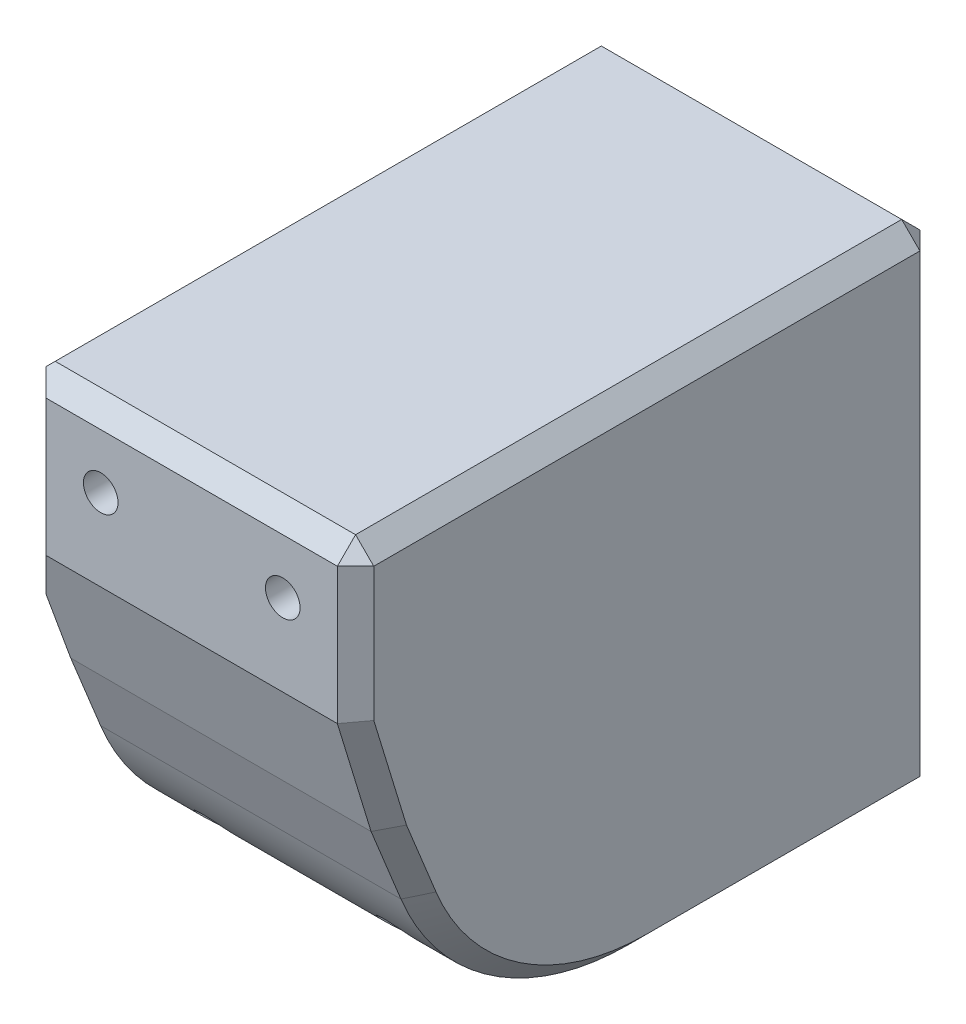
SolidWorks part; units mm, degrees
material "丙烯酸(中高冲击)"
ref_plane "前视基准面" through (0, 0, 0) normal (0, 0, 1) x (1, 0, 0)
ref_plane "上视基准面" through (0, 0, 0) normal (0, 1, 0) x (1, 0, 0)
ref_plane "右视基准面" through (0, 0, 0) normal (1, 0, 0) x (0, 0, -1)
sketch "草图1" plane through (0, 0, 0) normal (1, 0, 0) x (0, 0, -1)
  line L1 (-16, -13.5) -> (16, -13.5)
  line L2 (-16, -13.5) -> (-16, 13.5)
  line L3 (-16, 13.5) -> (16, 13.5)
  line L4 (16, -13.5) -> (16, 13.5)
  line L5 (-16, -13.5) -> (16, 13.5) construction
  line L6 (-16, 13.5) -> (16, -13.5) construction
  point P0 (0, 0)
  dimension "D1" = 32
  dimension "D2" = 27
extrude "凸台-拉伸1" add sketch "草图1" along normal blind 18
sketch "草图2" plane through (0, 0, 0) normal (-1, 0, 0) x (0, 0, 1)
  line L0 (0, 13.5) -> (0, -16.8118) construction
  line L1 (-16, 13.5) -> (16, 13.5) construction
  line L2 (-16, 0) -> (32.6294, 0) construction
  line L3 (-16, -13.5) -> (-16, 13.5) construction
  circle A0 centre (0, 0) radius 12.5
  dimension "D1" = 25
extrude "切除-拉伸1" cut sketch "草图2" against normal blind 13.5
sketch "草图3" plane through (13.5, 0, 0) normal (-1, 0, 0) x (0, 0, 1)
  circle A0 centre (0, 0) radius 3.5
  dimension "D1" = 7
extrude "切除-拉伸2" cut sketch "草图3" against normal offset from surface (4 mm away) 0.5 up to face at (18, 0, 0)
sketch "草图4" plane through (0, 0, -16) normal (0, 0, -1) x (-1, 0, 0)
  line L0 (-17.7262, 0) -> (0.9192, 0) construction
  line L1 (-9, 13.5) -> (-9, -17.0327) construction
  line L2 (-18, 13.5) -> (0, 13.5) construction
  line L3 (-18, -13.5) -> (-18, 13.5) construction
  circle A0 centre (-14, 9.5) radius 0.95
  circle A1 centre (-4, 9.5) radius 0.95
  circle A2 centre (-4, -9.5) radius 0.95
  circle A3 centre (-14, -9.5) radius 0.95
  dimension "D1" = 1.9
  dimension "D2" = 4
  dimension "D3" = 4
extrude "切除-拉伸3" cut sketch "草图4" against normal through all
sketch "草图6" plane through (0, 0, 0) normal (-1, 0, 0) x (0, 0, 1)
  line L0 (16, -13.5) -> (16, 3.5151)
  line L2 (16, -13.5) -> (0, -13.5)
  line L3 (16, -13.5) -> (-16, -13.5) construction
  line L5 (16, 3.5151) -> (12.507, -5.0817)
  line L6 (16, 13.5) -> (16, -13.5) construction
  arc A0 (0, -13.5) -> (12.507, -5.0817) centre (0, 0) ccw
extrude "切除-拉伸4" cut sketch "草图6" against normal through all
chamfer "倒角2" distance 1.5 angle 17 1 edges at (9, 3.5151, 16) first distance on face at (4.95, 9.5, 16)
chamfer "倒角3" distance 1 angle 45 12 edges at (18, 13.5, 0) (18, 0, -16) (9, 13.5, -16) (0, 0, -16) (9, -13.5, -16) (18, -13.5, -8) (18, -11.1994, 7.5381) (18, -3.0631, 13.3272) (18, 1.9853, 15.0737) (18, 9.2576, 16) (0, 9.2576, 16) (9, 13.5, 16)
chamfer "倒角4" distance 0.5 angle 45 6 edges at (0, 13.5, 0) (0, -3.0631, 13.3272) (0, -11.1994, 7.5381) (0, -13.5, -7.5) (0, 0, 12.5) (13.5, 0, 3.5)
